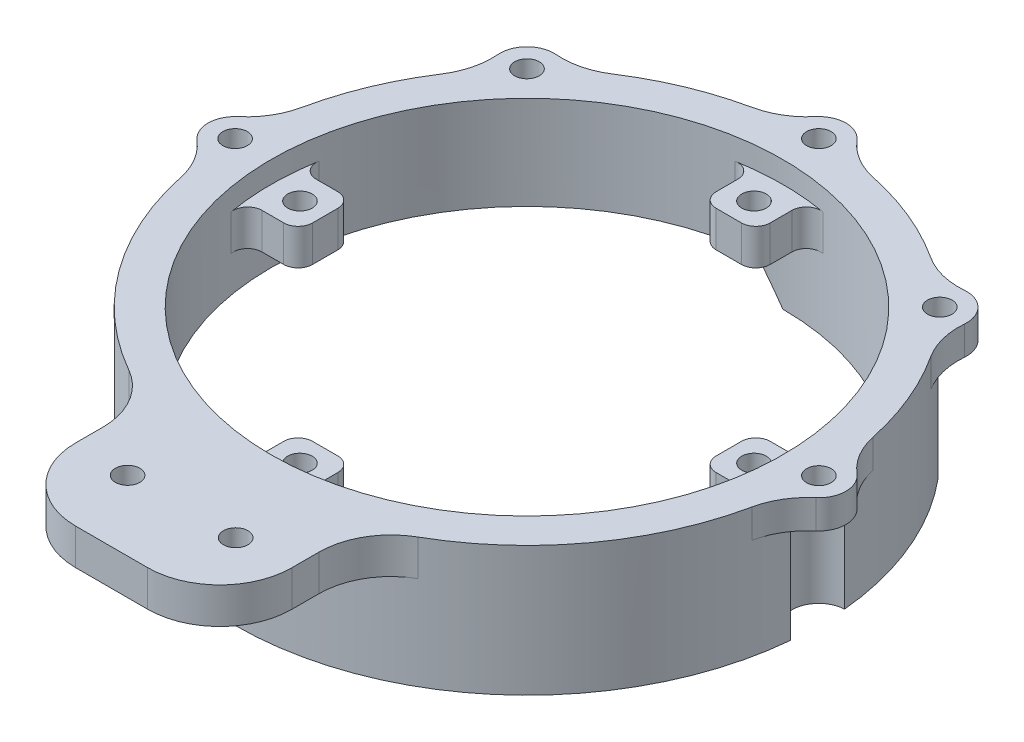
SolidWorks part; units mm, degrees
ref_plane "Alzado" through (0, 0, 0) normal (0, 0, 1) x (1, 0, 0)
ref_plane "Planta" through (0, 0, 0) normal (0, 1, 0) x (1, 0, 0)
ref_plane "Vista lateral" through (0, 0, 0) normal (1, 0, 0) x (0, 0, -1)
sketch "Croquis1" plane through (0, 0, 0) normal (0, 1, 0) x (1, 0, 0)
  circle A0 centre (0, 0) radius 35.5
  circle A1 centre (0, 0) radius 40.5
  dimension "D1" = 71
  dimension "D2" = 5
extrude "Saliente-Extruir1" add sketch "Croquis1" along normal mid plane 18
sketch "Croquis2" plane through (0, 9, 0) normal (0, -1, 0) x (1, 0, 0)
  line L0 (-15, 37.6198) -> (-15, 57.6198)
  line L1 (-15, 57.6198) -> (15, 57.6198)
  line L2 (15, 57.6198) -> (15, 37.6198)
  line L3 (0, 0) -> (0, 98.2113) construction
  circle A0 centre (0, 0) radius 40.5 construction
  arc A1 (15, 37.6198) -> (-15, 37.6198) centre (0, 0) ccw
  circle A2 centre (-7.5, 47.9166) radius 1.7
  circle A3 centre (7.5, 47.9166) radius 1.7
  circle A6 centre (0, 0) radius 48.5
  circle A7 centre (0, 0) radius 48.5 construction
  point P7 (0, 57.6198)
  dimension "D5" = 3.4
  dimension "D1" = 30
  dimension "D2" = 20
  dimension "D3" = 8
  dimension "D4" = 15
extrude "Saliente-Extruir2" add sketch "Croquis2" along normal blind 5
fillet "Redondeo1" radius 10 4 edges at (15, 6.5, 37.6198) (-15, 6.5, 37.6198) (-15, 6.5, 57.6198) (15, 6.5, 57.6198)
ref_plane "Plano1" through (0, 1, 0) normal (0, -1, 0) x (-1, 0, 0)
sketch "Croquis4" plane through (0, 1, 0) normal (0, -1, 0) x (-1, 0, 0)
  line L0 (0, -35.5) -> (0, 0) construction
  line L1 (-3.75, -35.3014) -> (-3.75, -28)
  line L2 (-3.75, -28) -> (3.75, -28)
  line L3 (3.75, -35.3014) -> (3.75, -28)
  circle A0 centre (0, 0) radius 35.5 construction
  arc A1 (-3.75, -35.3014) -> (3.75, -35.3014) centre (0, 0) ccw
  circle A2 centre (0, 0) radius 25 construction
  circle A3 centre (0, -31.5) radius 1.7
  circle A4 centre (0, 0) radius 31.5 construction
  point P12 (0, -28)
  dimension "D1" = 3.4
  dimension "D5" = 50
  dimension "D6" = 6.5
  dimension "D3" = 7.5
  dimension "D4" = 3.75
extrude "Saliente-Extruir3" add sketch "Croquis4" against normal blind 5
fillet "Redondeo2" radius 2 4 edges at (-3.75, 3.5, 35.3014) (3.75, 3.5, 28) (-3.75, 3.5, 28) (3.75, 3.5, 35.3014)
pattern_circular "MatrizC1" count 4 every 90 about axis through (0, 9, 0) along (0, 1, 0) of "Saliente-Extruir3", "Redondeo2"
hole_wizard "Refrentado para tornillo con cabeza plana de M31" positions "Croquis6" profile "Croquis7" counterbore size "M3" standard "ISO" end condition through all
sketch "Croquis6" plane through (0, -9, 0) normal (0, -1, 0) x (-1, 0, 0)
  circle A0 centre (0, 0) radius 40.5 construction
  point P0 (0, 40.5)
sketch "Croquis7" plane through (0, -9, -40.5) normal (1, 0, 0) x (0, 0, -1)
  line L0 (0, 0) -> (0, 18)
  line L1 (0, 18) -> (1.7, 18)
  line L3 (1.7, 18) -> (1.7, 14)
  line L4 (1.7, 14) -> (3.75, 14)
  line L5 (3.75, 14) -> (3.75, 0)
  line L7 (3.75, 0) -> (0, 0)
  line L11 (0, -6.35) -> (0, 107.95) construction
  dimension "Diámetro de taladro hasta el siguiente" = 3.4
  dimension "Profundidad de taladro hasta el siguiente" = 18
  dimension "Diámetro de refrentado" = 7.5
  dimension "Profundidad de refrentado" = 14
sketch "Croquis8" plane through (0, 9, 0) normal (0, 1, 0) x (1, 0, 0)
  circle A0 centre (0, 40.5) radius 3.75
  circle A1 centre (0, 40.5) radius 1.7
  arc A2 (-3.746, 40.3264) -> (3.746, 40.3264) centre (0, 40.5) ccw construction
  arc A3 (-3.746, 40.3264) -> (3.746, 40.3264) centre (0, 40.5) ccw construction
extrude "Saliente-Extruir4" add sketch "Croquis8" against normal up to surface (4 mm away) up to face at (0, 5, -39.0917)
pattern_circular "MatrizC2" count 3 every 45 about axis through (0, 9, 0) along (0, 1, 0) of "Saliente-Extruir4", "Refrentado para tornillo con cabeza plana de M31"
mirror "Simetría1" about plane through (0, 0, 0) normal (1, 0, 0) of "MatrizC2"
sketch "Croquis9" [suppressed] plane through (0, 9, 0) normal (0, 1, 0) x (1, 0, 0)
  line L0 (-36.7594, -17) -> (36.7594, -17)
  arc A0 (-40.3264, -3.746) -> (-20.0495, -35.189) centre (0, 0) ccw construction
  arc A1 (-36.7594, -17) -> (36.7594, -17) centre (0, 0) ccw
  dimension "D1" = 17
fillet "Redondeo3" radius 10 10 edges at (-40.3264, 7, -3.746) (-40.3264, 7, 3.746) (-31.1639, 7, -25.8663) (-25.8663, 7, -31.1639) (-3.746, 7, -40.3264) (3.746, 7, -40.3264) (31.1639, 7, -25.8663) (25.8663, 7, -31.1639) (40.3264, 7, -3.746) (40.3264, 7, 3.746)
sketch "Croquis10" plane through (0, -9, 0) normal (0, -1, 0) x (1, 0, 0)
  line L0 (0, 40.5) -> (0, 35.5)
  line L2 (0, -35.5) -> (0, -40.5)
  arc A2 (0, -40.5) -> (0, 40.5) centre (0, 0) cw
  arc A3 (0, -35.5) -> (0, 35.5) centre (0, 0) cw
extrude "Cortar-Extruir2" cut sketch "Croquis10" against normal blind 5
chamfer "Chaflán2" distance 5 angle 35 2 edges at (0, -4, 38) (0, -4, -36.125) first distance on face at (0, -6.5, 38) first distance on face at (0, -6.5, -36.125)
